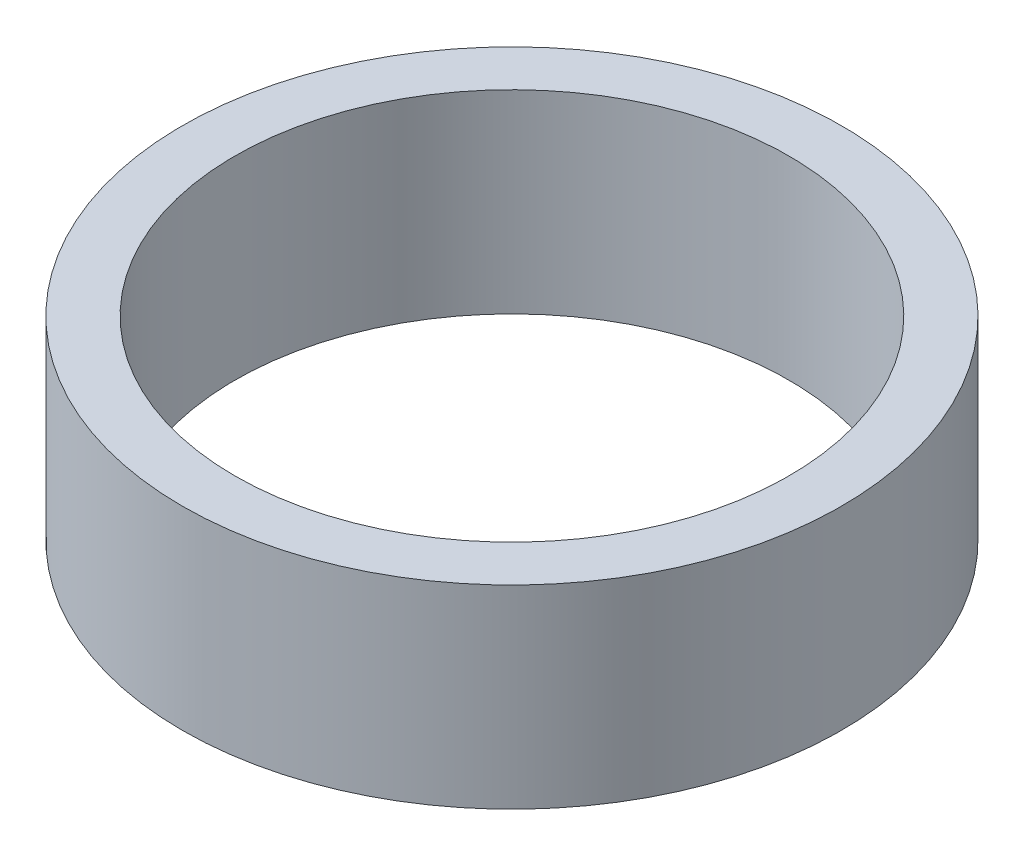
SolidWorks part; units mm, degrees
ref_plane "Front Plane" through (0, 0, 0) normal (0, 0, 1) x (1, 0, 0)
ref_plane "Top Plane" through (0, 0, 0) normal (0, 1, 0) x (1, 0, 0)
ref_plane "Right Plane" through (0, 0, 0) normal (1, 0, 0) x (0, 0, -1)
sketch "Sketch1" plane through (0, 0, 0) normal (0, 1, 0) x (1, 0, 0)
  circle A0 centre (0, 0) radius 63 construction
  circle A1 centre (0, 0) radius 62.8
  circle A2 centre (0, 0) radius 52.8
  dimension "D1" = 126
  dimension "D2" = 0.2
  dimension "D3" = 10
extrude "Boss-Extrude1" add sketch "Sketch1" along normal mid plane 37
